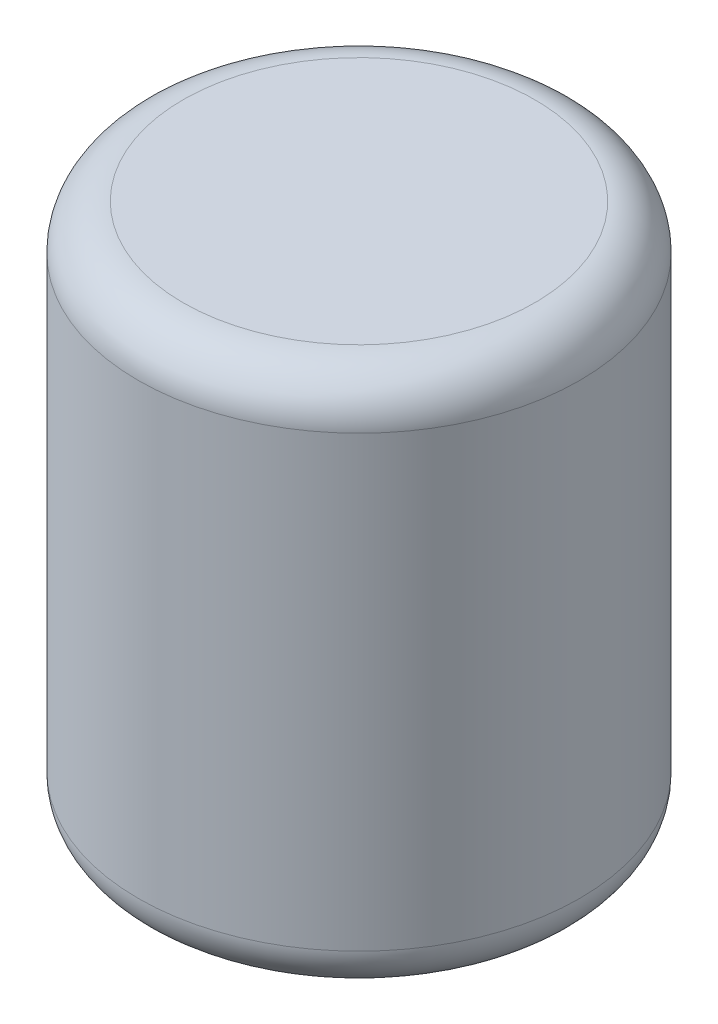
SolidWorks part; units mm, degrees
ref_plane "Front Plane" through (0, 0, 0) normal (0, 0, 1) x (1, 0, 0)
ref_plane "Top Plane" through (0, 0, 0) normal (0, 1, 0) x (1, 0, 0)
ref_plane "Right Plane" through (0, 0, 0) normal (1, 0, 0) x (0, 0, -1)
sketch "Sketch1" plane through (0, 0, 0) normal (0, 0, 1) x (1, 0, 0)
  line L0 (-1.4605, 0) -> (-1.4605, 4)
  line L1 (-1.4605, 4) -> (0, 4)
  line L2 (0, 4) -> (0, 6)
  line L3 (0, 6) -> (-2.4605, 6)
  line L4 (-2.4605, 6) -> (-2.4605, 0)
  line L5 (-2.4605, 0) -> (-1.4605, 0)
  line L6 (0, 0) -> (0, -1.3826) construction
  dimension "D2" = 2.921
  dimension "D3" = 6
  dimension "4" = 4
  dimension "1mm" = 1
revolve "Revolve1" add sketch "Sketch1" angle 360 about L6
fillet "Fillet1" radius 0.5 3 edges at (0, 6, 2.4605) (0, 0, 2.4605) (0, 0, 1.4605)
